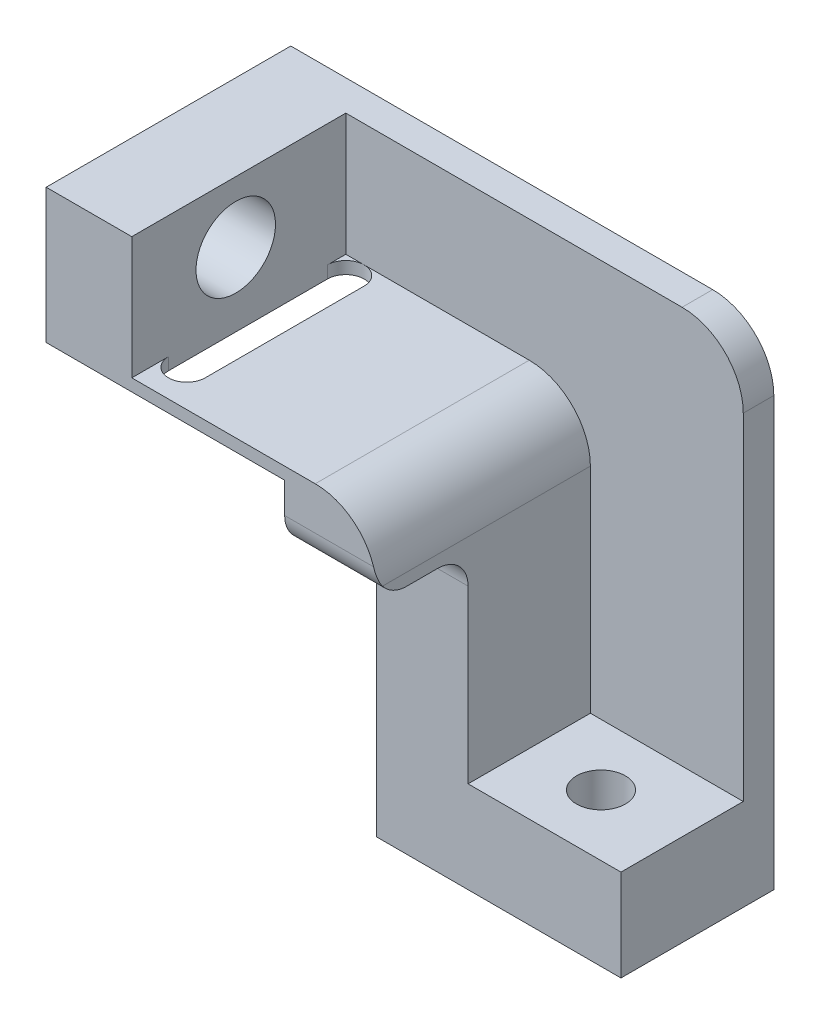
SolidWorks part; units mm, degrees
material "ABS"
ref_plane "Front Plane" through (0, 0, 0) normal (0, 0, 1) x (1, 0, 0)
ref_plane "Top Plane" through (0, 0, 0) normal (0, 1, 0) x (1, 0, 0)
ref_plane "Right Plane" through (0, 0, 0) normal (1, 0, 0) x (0, 0, -1)
sketch "Sketch1" plane through (0, 0, 0) normal (0, 0, 1) x (1, 0, 0)
  line L0 (40, -23.3254) -> (0, -23.3254)
  line L1 (0, -23.3254) -> (0, 34.6746)
  line L7 (15, 56.6746) -> (15, -8.3254)
  line L8 (15, -8.3254) -> (40, -8.3254)
  line L9 (40, -8.3254) -> (40, -23.3254)
  line L10 (15, 56.6746) -> (-39.0028, 56.6746)
  line L11 (-39.0028, 56.6746) -> (-39.0028, 34.6746)
  line L12 (-39.0028, 34.6746) -> (0, 34.6746)
  dimension "D1" = 40
  dimension "D2" = 80
  dimension "D3" = 22
  dimension "D4" = 15
  dimension "D5" = 15
extrude "Boss-Extrude1" add sketch "Sketch1" along normal blind 40
sketch "Sketch2" plane through (0, -8.3254, 0) normal (0, 1, 0) x (1, 0, 0)
  line L0 (40, 0) -> (15, 0) construction
  circle A0 centre (26.7302, -15) radius 4
  dimension "D1" = 8
  dimension "D2" = 15
extrude "Cut-Extrude1" cut sketch "Sketch2" against normal blind 30
sketch "Sketch3" plane through (-39.0028, 0, 0) normal (1, 0, 0) x (0, 0, -1)
  line L2 (-40, -8.3254) -> (-40, 56.6746) construction
  line L3 (-40, 56.6746) -> (0, 56.6746) construction
  circle A0 centre (-23, 46.6746) radius 6.5
  dimension "D1" = 17
  dimension "D2" = 13
  dimension "D3" = 10
extrude "Cut-Extrude2" cut sketch "Sketch3" along normal blind 100 and the other way blind 100
sketch "Sketch5" plane through (15, 0, 0) normal (1, 0, 0) x (0, 0, -1)
  line L0 (-40, 56.6746) -> (0, 56.6746) construction
  line L1 (-40, 56.6746) -> (-5, 56.6746)
  line L2 (-40, 56.6746) -> (-40, 36.6746)
  line L3 (-40, 36.6746) -> (-5, 36.6746)
  line L4 (-5, 56.6746) -> (-5, 36.6746)
  line L5 (-40, -8.3254) -> (-40, 56.6746) construction
  line L6 (0, -8.3254) -> (0, 56.6746) construction
  dimension "D1" = 20
  dimension "D2" = 5
extrude "Cut-Extrude3" cut sketch "Sketch5" against normal blind 40
sketch "Sketch6" plane through (15, 0, 0) normal (1, 0, 0) x (0, 0, -1)
  line L0 (0, -8.3254) -> (0, 56.6746) construction
  line L1 (-5, 56.6746) -> (0, 56.6746)
  line L2 (-5, 56.6746) -> (-5, -8.3254)
  line L3 (-5, -8.3254) -> (0, -8.3254)
  line L4 (0, 56.6746) -> (0, -8.3254)
  line L5 (-40, -8.3254) -> (0, -8.3254) construction
extrude "Boss-Extrude2" add sketch "Sketch6" along normal blind 25
sketch "Sketch7" plane through (0, 36.6746, 0) normal (0, 1, 0) x (1, 0, 0)
  line L0 (-22, -8) -> (-22, -34) construction
  line L1 (-19, -8) -> (-19, -34)
  line L2 (-25, -8) -> (-25, -34)
  line L3 (-25, -40) -> (-25, -5) construction
  line L4 (-25, -5) -> (15, -5) construction
  line L5 (15, -40) -> (-25, -40) construction
  arc A0 (-19, -8) -> (-25, -8) centre (-22, -8) ccw
  arc A1 (-25, -34) -> (-19, -34) centre (-22, -34) ccw
  point P2 (-22, -21)
  dimension "D2" = 3
  dimension "D1" = 3
  dimension "D3" = 3
  dimension "D4" = 6
extrude "Cut-Extrude4" cut sketch "Sketch7" against normal blind 10
fillet "Fillet1" radius 10 2 edges at (15, 36.6746, 22.5) (40, 56.6746, 2.5)
sketch "Sketch8" plane through (0, 0, 40) normal (0, 0, 1) x (1, 0, 0)
  line L0 (0, 34.6746) -> (0, -23.3254) construction
  line L1 (40, -23.3254) -> (0, -23.3254)
  line L2 (40, -23.3254) -> (40, 24.6746)
  line L3 (40, 24.6746) -> (0, 24.6746)
  line L4 (0, -23.3254) -> (0, 24.6746)
  line L5 (-39.0028, 34.6746) -> (0, 34.6746) construction
  dimension "D1" = 10
extrude "Cut-Extrude5" cut sketch "Sketch8" against normal blind 15
fillet "Fillet2" radius 5 2 edges at (7.5, 24.6746, 40) (7.5, 24.6746, 25)
